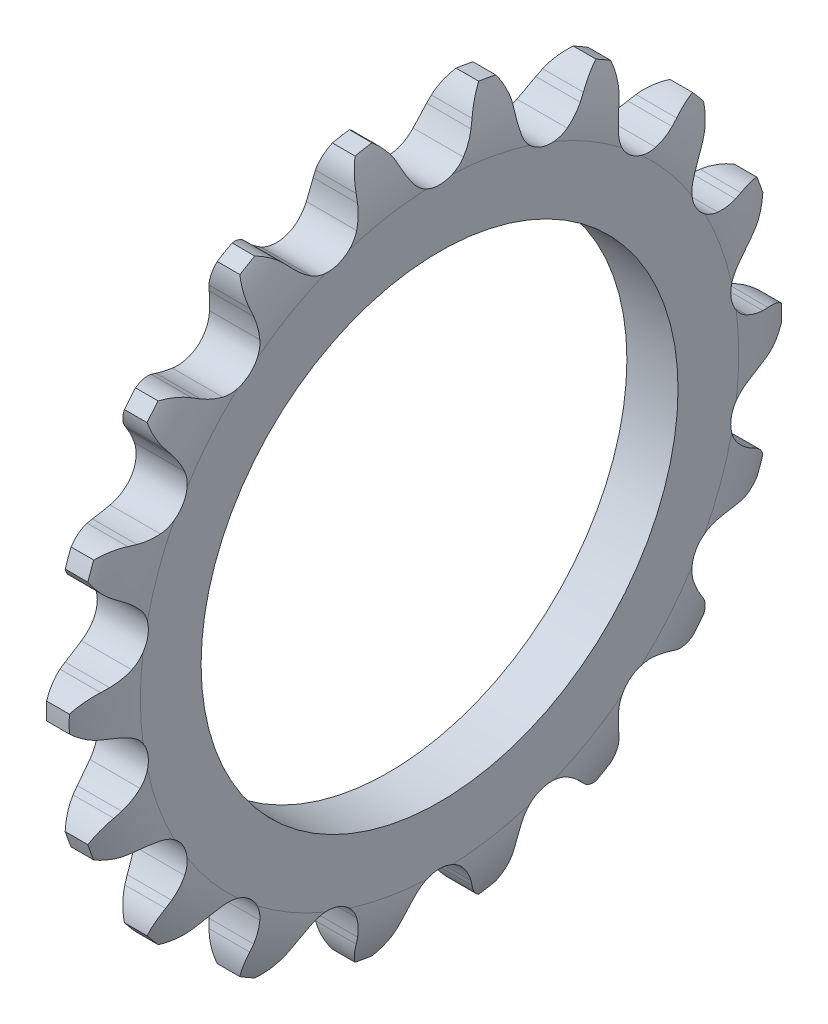
SolidWorks part; units mm, degrees
ref_plane "Plane1" through (0, 0, 0) normal (0, 0, 1) x (1, 0, 0)
ref_plane "Plane2" through (0, 0, 0) normal (0, 1, 0) x (1, 0, 0)
ref_plane "Plane3" through (0, 0, 0) normal (1, 0, 0) x (0, 0, -1)
other "Configuration Table"
sketch "Clipboard" plane through (0, 0, 0) normal (0, 1, 0) x (1, 0, 0)
  line L0 (0, 0) -> (9.0588, -2.9434)
  line L1 (-15, 0) -> (100, 0) construction
  line L2 (0, 0) -> (-0.7911, 0.8941)
  line L3 (0, 0) -> (-4.4605, 1.7048)
  line L4 (0, 0) -> (4.5415, 1.4756)
  line L5 (0, 0) -> (-47.5972, -17.7524)
  line L6 (0, 0) -> (-3.555, -2.3986)
  line L7 (-0.7911, 0.8941) -> (47.2413, 17.433)
  line L8 (-76.2, 38.1) -> (-58.1914, 38.1)
  line L9 (-73.2057, 38.5609) -> (-73.0533, 38.5634)
  line L10 (-73.0533, 76.1892) -> (-62.9187, 76.1892)
  circle A0 centre (0, 0) radius 2.54
  circle A1 centre (0, 0) radius 21.866
  circle A2 centre (0, 0) radius 38.1
  dimension "Num_teeth" = 18
  dimension "Thickness" = 4.2885
sketch "BasProSke" plane through (0, 0, 0) normal (0, 1, 0) x (1, 0, 0)
  line L0 (-10, 0) -> (60, 0) construction
  line L1 (0, 0) -> (0, 25.0918)
  line L2 (0, 0) -> (4.2885, 0)
  line L3 (4.2885, 0) -> (4.2885, 25.0918)
  line L4 (3.0947, 29.867) -> (1.1938, 29.867)
  arc A0 (0, 25.0918) -> (1.1938, 29.867) centre (10.1473, 25.0918) cw
  arc A1 (4.2885, 25.0918) -> (3.0947, 29.867) centre (-5.8588, 25.0918) ccw
  dimension "D1" = 10.1473
  dimension "Thickness" = 4.2885
  dimension "Diameter" = 59.734
  dimension "H1" = 4.7752
  dimension "G1" = 1.1938
revolve "Base-Revolve" add sketch "BasProSke" angle 360 about L0
sketch "GrvSke" plane through (0, 0, 0) normal (0, 1, 0) x (1, 0, 0)
  line L0 (4.2885, 25.0918) -> (4.2885, 21.866)
  line L1 (4.2885, 21.866) -> (10.1346, 21.866)
  line L2 (10.1346, 21.866) -> (10.1346, 25.0918)
  line L3 (3.0947, 29.867) -> (11.3284, 29.867)
  line L4 (7.2116, 0) -> (7.2116, 52.07) construction
  line L5 (-10, 0) -> (60, 0) construction
  line L6 (0, 0) -> (35.56, 0) construction
  arc A0 (10.1346, 25.0918) -> (11.3284, 29.867) centre (20.2819, 25.0918) cw
  arc A1 (4.2885, 25.0918) -> (3.0947, 29.867) centre (-5.8588, 25.0918) ccw
  dimension "Diameter" = 59.734
  dimension "H1" = 4.7752
  dimension "G1" = 1.1938
revolve "Groove" [suppressed] cut sketch "GrvSke" angle 360 about L6
pattern_linear "Grooves" [suppressed]
sketch "TooCutSke" plane through (0, 0, 0) normal (1, 0, 0) x (0, 0, -1)
  line L0 (2.9176, 27.2991) -> (3.16, 27.8581)
  line L1 (0, 0) -> (0, 107) construction
  line L2 (0, 27.4261) -> (-10, 27.4261) construction
  line L3 (-2.9176, 27.2991) -> (-3.16, 27.8581)
  arc A0 (2.0323, 25.8192) -> (2.9176, 27.2991) centre (-3.1879, 29.9468) ccw
  arc A1 (2.0323, 25.8192) -> (-2.0323, 25.8192) centre (0, 27.4261) cw
  arc A2 (3.16, 27.8581) -> (7.004, 30.381) centre (7.004, 26.1912) cw
  arc A3 (-2.0323, 25.8192) -> (-2.9176, 27.2991) centre (3.1879, 29.9468) cw
  arc A4 (-3.16, 27.8581) -> (-7.004, 30.381) centre (-7.004, 26.1912) ccw
  arc A5 (7.004, 30.381) -> (-7.004, 30.381) centre (0, 0) ccw
  dimension "Pitch_radius" = 27.4261
  dimension "V" = 1.235
extrude "ToothCut" cut sketch "TooCutSke" along normal through all
pattern_circular "TeethCuts" count 18 over 360 about axis through (-10, 0, 0) along (1, 0, 0) of "ToothCut"
sketch "HubNeaOneSke" plane through (0, 0, 0) normal (-1, 0, 0) x (0, 0, 1)
  circle A0 centre (0, 0) radius 21.866
  dimension "Diameter" = 43.732
extrude "HubNearOne" [suppressed] add sketch "HubNeaOneSke" along normal blind 46.5115
sketch "HubNeaBotSke" plane through (0, 0, 0) normal (-1, 0, 0) x (0, 0, 1)
  circle A0 centre (0, 0) radius 21.866
  dimension "Diameter" = 43.732
extrude "HubNearBoth" [suppressed] add sketch "HubNeaBotSke" along normal blind 23.2558
ref_plane "FarPln" through (4.2885, 0, 0) normal (1, 0, 0) x (0, 0, -1)
sketch "HubFarSke" plane through (4.2885, 0, 0) normal (1, 0, 0) x (0, 0, -1)
  circle A0 centre (0, 0) radius 21.866
  dimension "Diameter" = 43.732
extrude "HubFar" [suppressed] add sketch "HubFarSke" along normal blind 23.2558
sketch "BorSke" plane through (0, 0, 0) normal (1, 0, 0) x (0, 0, -1)
  circle A0 centre (0, 0) radius 20
  dimension "Diameter" = 40
extrude "Bore" cut sketch "BorSke" along normal mid plane 101.6001
sketch "KeySke" plane through (0, 0, 0) normal (1, 0, 0) x (0, 0, -1)
  line L0 (-2.3813, 0) -> (-2.3813, -1.9914)
  line L1 (-2.3813, -1.9914) -> (2.3813, -1.9914)
  line L2 (2.3813, -1.9914) -> (2.3813, 0)
  line L3 (0, 0) -> (0, 34) construction
  line L4 (-2.3813, 0) -> (2.3813, 0)
  dimension "Offset" = 1.9914
  dimension "Width" = 4.7625
extrude "Keyway" [suppressed] cut sketch "KeySke" along normal mid plane 101.6001
pattern_circular "Keyway2" [suppressed] count 2 every 90 about axis through (-10, 0, 0) along (1, 0, 0) reverse direction yes
sketch "Sketch1" plane through (4.2885, 0, 0) normal (1, 0, 0) x (0, 0, -1)
  circle A0 centre (0, 0) radius 9.4843
ref_plane "MIDPLANE" through (2.1443, 0, 0) normal (1, 0, 0) x (0, 0, -1)
equation "\"Num_teeth@Clipboard\" = int( \"Num_teeth@Clipboard\" )"
equation "\"Num_teeth@Clipboard\" = ((sgn( \"Num_teeth@Clipboard\" - 5.0)+1)*( \"Num_teeth@Clipboard\" - 5.0))/2 +5.0"
equation "\"Num_teeth@Clipboard\" = ((sgn( \"Num_teeth@Clipboard\" - 200.0)-1)*( \"Num_teeth@Clipboard\" - 200.0))/-2 +200.0"
equation "\"MHD@Clipboard\" = \"Pitch@Clipboard\" * (1.0 / tan(3.14159265 / \"Num_teeth@Clipboard\" ) - 1.0) - 0.03"
equation "\"Thickness@Clipboard\"  = \"Width@Clipboard\" * \"Width_factor@Clipboard\" - \"Width_const@Clipboard\" + (\"Num_strands@Clipboard\" - 1) * \"Transv_pitch@Clipboard\""
equation "\"OAL@Clipboard\" = \"Thickness@Clipboard\""
equation "\"MHD@Clipboard\" = ((sgn( \"MHD@Clipboard\" - \"Hub_dia@Clipboard\" )-1)*( \"MHD@Clipboard\" - \"Hub_dia@Clipboard\" ))/-2+ \"Hub_dia@Clipboard\""
equation "\"OAL@Clipboard\" = ((sgn( \"OAL@Clipboard\" - \"Overall_len@Clipboard\" )+1)*( \"OAL@Clipboard\" - \"Overall_len@Clipboard\" ))/2 + \"Overall_len@Clipboard\" + 0.000002"
equation "\"Num_teeth@TeethCuts\" = int( \"Show_teeth@Clipboard\" ) + 1"
equation "\"Num_teeth@TeethCuts\" = ((sgn( \"Num_teeth@TeethCuts\" - \"Num_teeth@Clipboard\" )-1)*( \"Num_teeth@TeethCuts\" - \"Num_teeth@Clipboard\" ))/-2+ \"Num_teeth@Clipboard\""
equation "\"Num_teeth@TeethCuts\" = ((sgn( \"Num_teeth@TeethCuts\" - 2.0)+1)*( \"Num_teeth@TeethCuts\" - 2.0))/2 +2.0"
equation "\"Angle@TeethCuts\" = 360.0 / \"Num_teeth@Clipboard\""
equation "\"Pitch_radius@TooCutSke\" = ( \"Pitch@Clipboard\" / 2.0) / sin(3.14159265 / \"Num_teeth@Clipboard\" )  'ma"
equation "\"R@TooCutSke\"  = \"Dr@Clipboard\" * 0.5025 + 0.0015"
equation "\"A@TooCutSke\" = 35.0 + (60.0 / \"Num_teeth@Clipboard\")"
equation "\"E@TooCutSke\"  = \"Dr@Clipboard\" * 1.3025 + 0.0015"
equation "\"B@TooCutSke\"  = 18.0 - (56.0 / \"Num_teeth@Clipboard\" )"
equation "\"W@TooCutSke\" = 1.4 * \"Dr@Clipboard\" * cos(3.14159265 / \"Num_teeth@Clipboard\" )"
equation "\"V@TooCutSke\" = 1.4 * \"Dr@Clipboard\" * sin(3.14159265 / \"Num_teeth@Clipboard\" )"
equation "\"Diameter@BasProSke\" = 2.0 * ( (0.3 * \"Pitch@Clipboard\" ) +  \"Pitch@Clipboard\" / 2.0 / tan(3.14159265 / \"Num_teeth@Clipboard\" ))"
equation "\"Thickness@BasProSke\"  = \"Thickness@Clipboard\""
equation "\"G1@BasProSke\" =  \"Chamfer_wid@Clipboard\""
equation "\"G2@BasProSke\" =  \"Chamfer_wid@Clipboard\""
equation "\"H1@BasProSke\" =  \"Chamfer_dep@Clipboard\""
equation "\"H2@BasProSke\" =  \"Chamfer_dep@Clipboard\""
equation "\"Diameter@GrvSke\" = \"Diameter@BasProSke\""
equation "\"G1@GrvSke\" = \"Chamfer_wid@Clipboard\""
equation "\"H1@GrvSke\" = \"Chamfer_dep@Clipboard\""
equation "\"Grv_diam@GrvSke\" =  \"Pitch@Clipboard\" * (1.0 / tan(3.14159265 / \"Num_teeth@Clipboard\" ) - 1.0) - 0.03"
equation "\"Grv_width@GrvSke\" =  \"Transv_pitch@Clipboard\" - ( \"Width@Clipboard\" * \"Width_factor@Clipboard\" - \"Width_const@Clipboard\" )"
equation "\"Offset@GrvSke\" = \"Grv_width@GrvSke\" / 2.0 + ( \"Width@Clipboard\" * \"Width_factor@Clipboard\" - \"Width_const@Clipboard\" )"
equation "\"Offset@Grooves\" = \"Transv_pitch@Clipboard\""
equation "\"Num_grvs@Grooves\" = \"Num_strands@Clipboard\""
equation "\"Num_grvs@Grooves\" = \"Num_grvs@Grooves\" - 1 * sgn( \"Num_grvs@Grooves\" -1)"
equation "\"Diameter@HubNeaOneSke\" = \"MHD@Clipboard\""
equation "\"Length@HubNearOne\" = \"OAL@Clipboard\" - \"Thickness@BasProSke\""
equation "\"Diameter@HubNeaBotSke\" = \"MHD@Clipboard\""
equation "\"Length@HubNearBoth\" = ( \"OAL@Clipboard\" - \"Thickness@BasProSke\" ) / 2.0"
equation "\"Thickness@FarPln\" = \"Thickness@BasProSke\""
equation "\"Diameter@HubFarSke\" = \"MHD@Clipboard\""
equation "\"Length@HubFar\" = ( \"OAL@Clipboard\" - \"Thickness@BasProSke\" ) / 2.0"
equation "\"D1@Bore\" = \"OAL@Clipboard\" * 2.0"
equation "\"D1@Keyway\" = \"OAL@Clipboard\" * 2.0"
equation "\"Offset@KeySke\" = \"T_dim@Clipboard\" - \"Diameter@BorSke\" / 2.0"
